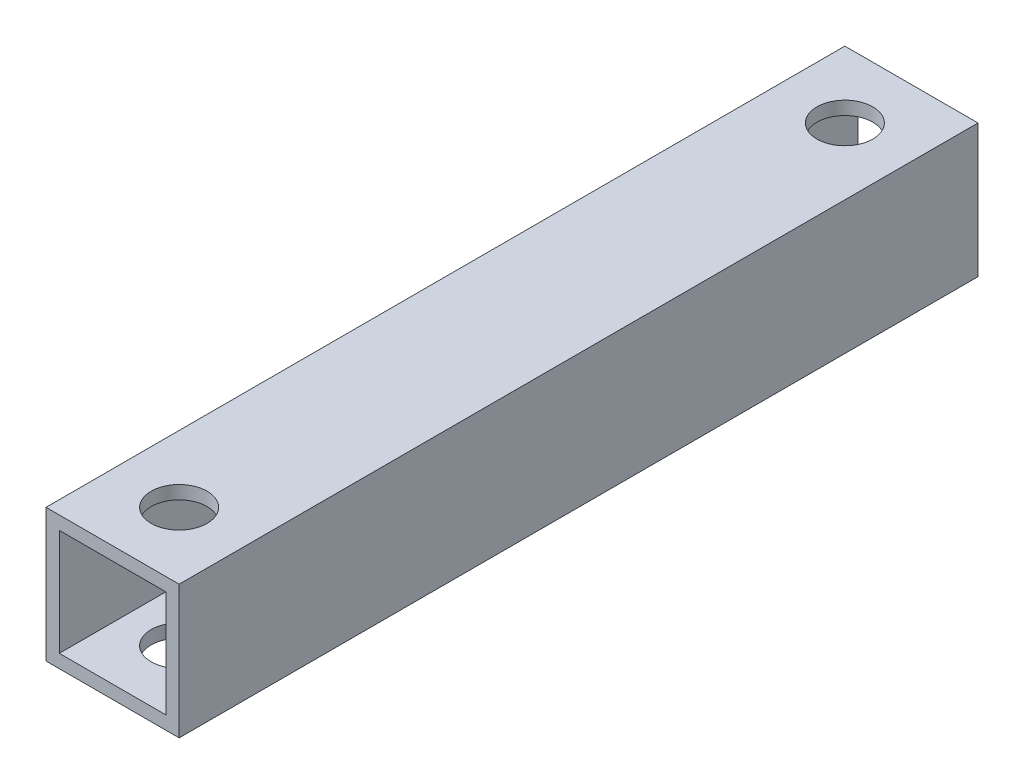
SolidWorks part; units mm, degrees
ref_plane "正面" through (0, 0, 0) normal (0, 0, 1) x (1, 0, 0)
ref_plane "平面" through (0, 0, 0) normal (0, 1, 0) x (1, 0, 0)
ref_plane "右側面" through (0, 0, 0) normal (1, 0, 0) x (0, 0, -1)
sketch "ｽｹｯﾁ1" plane through (0, 0, 0) normal (0, 0, 1) x (1, 0, 0)
  line L0 (-4, 4) -> (-4, -4)
  line L1 (-5, 5) -> (5, 5)
  line L2 (-5, 5) -> (-5, -5)
  line L3 (-5, -5) -> (5, -5)
  line L4 (5, 5) -> (5, -5)
  line L5 (-5, 5) -> (5, -5) construction
  line L6 (-5, -5) -> (5, 5) construction
  line L7 (-4, -4) -> (4, -4)
  line L8 (4, 4) -> (4, -4)
  line L9 (-4, 4) -> (4, 4)
  point P0 (0, 0)
  dimension "D1" = 10
  dimension "D2" = 10
  dimension "D3" = 1
extrude "ﾎﾞｽ - 押し出し1" add sketch "ｽｹｯﾁ1" along normal blind 60
sketch "ｽｹｯﾁ2" plane through (0, 5, 0) normal (0, 1, 0) x (1, 0, 0)
  line L0 (5, 0) -> (-5, 0) construction
  line L1 (5, -60) -> (-5, -60) construction
  circle A0 centre (0, -5) radius 2.1
  circle A1 centre (0, -55) radius 2.1
  dimension "D1" = 5
  dimension "D2" = 4.2
  dimension "D3" = 5
  dimension "D4" = 4.2
extrude "ｶｯﾄ - 押し出し1" cut sketch "ｽｹｯﾁ2" against normal blind 40
